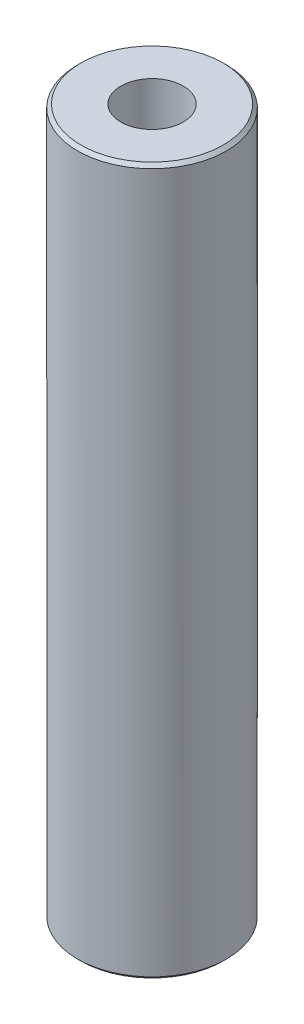
SolidWorks part; units mm, degrees
ref_plane "Front Plane" through (0, 0, 0) normal (0, 0, 1) x (1, 0, 0)
ref_plane "Top Plane" through (0, 0, 0) normal (0, 1, 0) x (1, 0, 0)
ref_plane "Right Plane" through (0, 0, 0) normal (1, 0, 0) x (0, 0, -1)
sketch "Sketch1" plane through (0, 0, 0) normal (0, 1, 0) x (1, 0, 0)
  circle A0 centre (0, 0) radius 10
  dimension "SHAFT_OD" = 20
extrude "Boss-Extrude1" add sketch "Sketch1" along normal blind 94.8356
sketch "Sketch2" plane through (0, 0, 0) normal (0, 1, 0) x (1, 0, 0)
  circle A0 centre (0, 0) radius 4.1886
  dimension "BORE_D" = 8.3772
extrude "Cut-Extrude1" cut sketch "Sketch2" along normal through all
chamfer "Chamfer1" distance 0.4504 angle 45 2 edges at (0, 94.8356, 10) (0, 0, 10)
